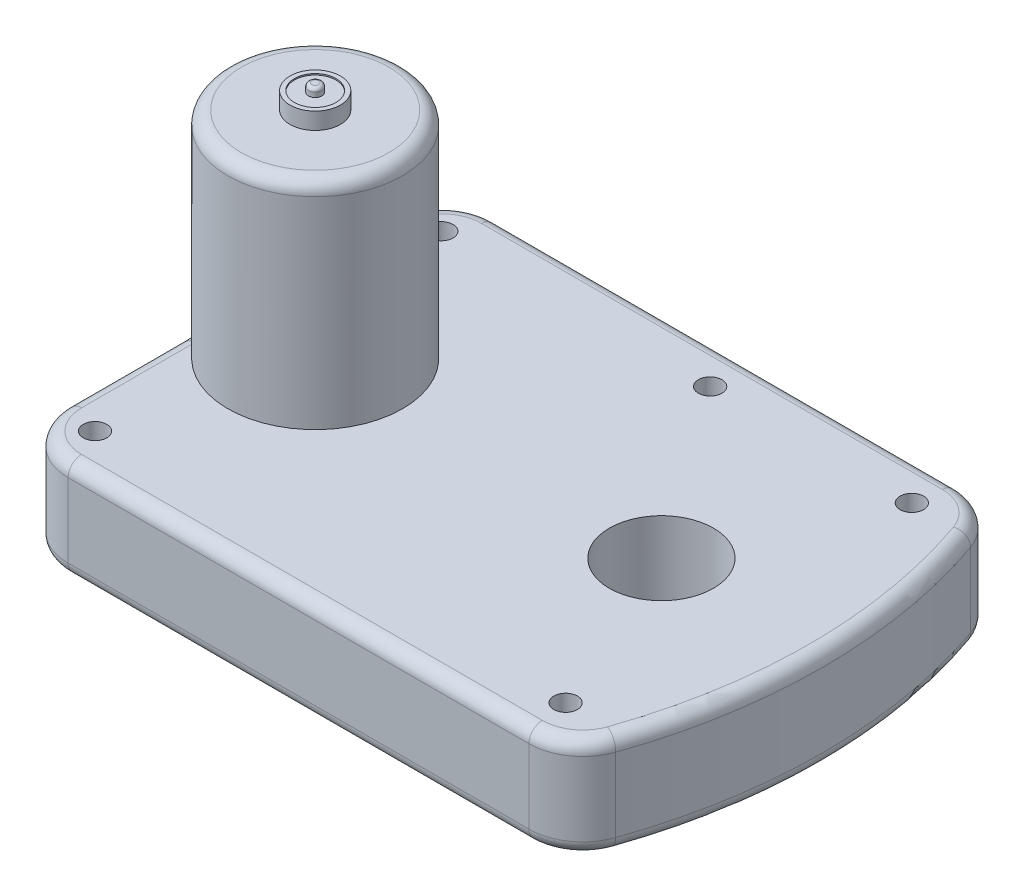
SolidWorks part; units mm, degrees
ref_plane "Front Plane" through (0, 0, 0) normal (0, 0, 1) x (1, 0, 0)
ref_plane "Top Plane" through (0, 0, 0) normal (0, 1, 0) x (1, 0, 0)
ref_plane "Right Plane" through (0, 0, 0) normal (1, 0, 0) x (0, 0, -1)
sketch "Sketch1" plane through (0, 0, 0) normal (0, 1, 0) x (1, 0, 0)
  line L0 (6, 57.5) -> (76, 57.5) construction
  line L1 (0, 0) -> (82, 0)
  line L2 (0, 0) -> (0, 63.5)
  line L3 (0, 63.5) -> (82, 63.5)
  line L4 (82, 0) -> (82, 63.5) construction
  line L5 (6, 6) -> (76, 6) construction
  line L6 (6, 57.5) -> (6, 6) construction
  line L7 (64.5, 31.75) -> (64.5, 63.5) construction
  line L8 (64.5, 31.75) -> (64.5, 0) construction
  line L10 (76, 57.5) -> (74.8448, 56.1854) construction
  line L12 (46.7887, 55.9378) -> (46, 57.5) construction
  line L13 (74.8448, 7.3146) -> (76, 6) construction
  circle A0 centre (6, 57.5) radius 1.75
  circle A1 centre (76, 57.5) radius 1.75
  circle A2 centre (6, 6) radius 1.75
  circle A3 centre (76, 6) radius 1.75
  circle A4 centre (46, 57.5) radius 1.75
  circle A5 centre (64.5, 31.75) radius 7.75
  arc A6 (82, 0) -> (82, 63.5) centre (8.5702, 31.75) ccw
  dimension "D3" = 64.5
  dimension "D4" = 3.5
  dimension "D6" = 6
  dimension "D2" = 6
  dimension "D8" = 30
  dimension "D9" = 15.5
  dimension "D10" = 80
  dimension "D1" = 63.5
  dimension "D5" = 6
  dimension "D7" = 6
  dimension "D11" = 82
extrude "Boss-Extrude1" add sketch "Sketch1" along normal blind 15
sketch "Sketch2" plane through (0, 0, 0) normal (0, -1, 0) x (1, 0, 0)
  line L0 (66, -17.75) -> (72.9821, -26.25)
  line L1 (49, -17.75) -> (66, -17.75)
  line L2 (49, -17.75) -> (49, -45.75)
  line L3 (49, -45.75) -> (66, -45.75)
  line L4 (72.9821, -26.25) -> (72.9821, -37.25)
  line L5 (72.9821, -26.25) -> (72.9821, -37.25)
  line L6 (72.9821, -37.25) -> (66, -45.75)
  line L7 (49, -17.75) -> (49, 0) construction
  line L8 (0, 0) -> (82, 0) construction
  line L9 (49, -45.75) -> (49, -63.5) construction
  line L10 (82, -63.5) -> (0, -63.5) construction
  line L11 (0, -63.5) -> (0, 0) construction
  circle A0 centre (64.5, -31.75) radius 7.75
  circle A1 centre (64.5, -31.75) radius 7.75 construction
  circle M18 centre (64.5, -31.75) radius 7.75
  dimension "D1" = 28
  dimension "D2" = 17
  dimension "D3" = 11
  dimension "D4" = 11
  dimension "D5" = 49
extrude "Boss-Extrude2" add sketch "Sketch2" along normal blind 9 contours L6 L4 L0 L1 L2 L3 M18 region at (69.2062, 0, -22.234)
sketch "Sketch3" plane through (49, 0, 0) normal (-1, 0, 0) x (0, 0, 1)
  line L1 (-17.75, 0) -> (-23.25, 0)
  line L2 (-17.75, 0) -> (-17.75, -7)
  line L3 (-17.75, -7) -> (-23.25, -7)
  line L4 (-23.25, 0) -> (-23.25, -7)
  line L5 (-45.75, 0) -> (-40.25, 0)
  line L6 (-45.75, 0) -> (-45.75, -7)
  line L7 (-45.75, -7) -> (-40.25, -7)
  line L8 (-40.25, 0) -> (-40.25, -7)
  dimension "D1" = 5.5
  dimension "D2" = 7
extrude "Cut-Extrude1" cut sketch "Sketch3" against normal through all
sketch "Sketch4" plane through (0, -9, 0) normal (0, -1, 0) x (1, 0, 0)
  line L0 (49, -17.75) -> (49, -45.75) construction
  line L1 (59.9931, -24.25) -> (50, -24.25)
  line L3 (59.9931, -39.25) -> (50, -39.25)
  line L4 (50, -24.25) -> (50, -39.25)
  line L5 (70.5178, -23.25) -> (49, -23.25) construction
  line L6 (70.5178, -40.25) -> (49, -40.25) construction
  arc A0 (59.9931, -24.25) -> (59.9931, -39.25) centre (64.5, -31.75) ccw
  circle A1 centre (64.5, -31.75) radius 7.75 construction
  dimension "D1" = 1
  dimension "D2" = 1
  dimension "D3" = 1
  dimension "D4" = 1
extrude "Cut-Extrude2" cut sketch "Sketch4" against normal up to surface (9 mm away) up to face at (42.6425, 0, -31.75)
sketch "Sketch5" plane through (0, 15, 0) normal (0, 1, 0) x (1, 0, 0)
  line L0 (13, 31.75) -> (6, 6) construction
  line L1 (13, 31.75) -> (6, 57.5) construction
  line L2 (0, 63.5) -> (0, 0) construction
  circle A0 centre (13, 31.75) radius 13
  dimension "D1" = 26
extrude "Boss-Extrude3" add sketch "Sketch5" along normal blind 32
sketch "Sketch6" plane through (0, 47, 0) normal (0, 1, 0) x (1, 0, 0)
  circle A0 centre (13, 31.75) radius 3.75
  circle A1 centre (13, 31.75) radius 13 construction
  dimension "D1" = 7.5
extrude "Boss-Extrude4" add sketch "Sketch6" along normal blind 2.5
sketch "Sketch7" plane through (0, 49.5, 0) normal (0, 1, 0) x (1, 0, 0)
  circle A0 centre (13, 31.75) radius 1
  dimension "D1" = 2
extrude "Boss-Extrude5" add sketch "Sketch7" along normal blind 1
fillet "Fillet2" radius 2 1 edges at (13, 47, -18.75)
sketch "Sketch10" plane through (0, 49.5, 0) normal (0, 1, 0) x (1, 0, 0)
  circle A0 centre (13, 31.75) radius 1
  circle A1 centre (13, 31.75) radius 1 construction
  circle A2 centre (13, 31.75) radius 3.0921
extrude "Cut-Extrude4" cut sketch "Sketch10" against normal blind 0.2
fillet "Fillet3" radius 0.5 1 edges at (13, 50.5, -30.75)
fillet "Fillet4" radius 8 4 edges at (82, 7.5, -63.5) (0, 7.5, -63.5) (0, 7.5, 0) (82, 7.5, 0)
fillet "Fillet5" radius 2 17 edges at (81.1711, 0, -1.4765) (42.2702, 0, 0) (2.3431, 0, -2.3431) (0, 0, -31.75) (2.3431, 0, -61.1569) (42.2702, 0, -63.5) (81.1711, 0, -62.0235) (81.1711, 15, -1.4765) (42.2702, 15, 0) (2.3431, 15, -2.3431) (0, 15, -19.875) (0, 15, -43.625) (2.3431, 15, -61.1569) (42.2702, 15, -63.5) (81.1711, 15, -62.0235) (88.5702, 0, -31.75) (88.5702, 15, -31.75)
fillet "Fillet7" radius 1 2 edges at (72.9821, -4.5, -26.25) (72.9821, -4.5, -37.25)
sketch "Sketch14" plane through (0, 0, 0) normal (0, -1, 0) x (1, 0, 0)
  line L0 (46, -6) -> (46, -57.5) construction
  line L1 (46, -6) -> (76, -6) construction
  circle A0 centre (46, -6) radius 1.75
  circle A1 centre (6, -6) radius 1.75 construction
extrude "Cut-Extrude6" cut sketch "Sketch14" against normal blind 10
sketch "Croquis1" plane through (0, 0, 0) normal (0, -1, 0) x (1, 0, 0)
